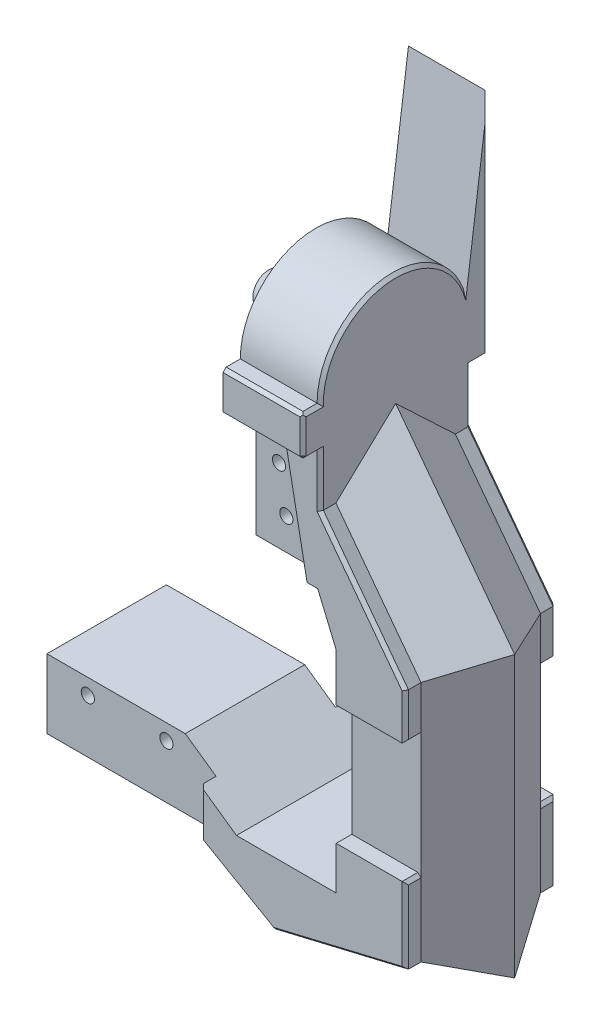
SolidWorks part; units mm, degrees
ref_plane "前视基准面" through (0, 0, 0) normal (0, 0, 1) x (1, 0, 0)
ref_plane "上视基准面" through (0, 0, 0) normal (0, 1, 0) x (1, 0, 0)
ref_plane "右视基准面" through (0, 0, 0) normal (1, 0, 0) x (0, 0, -1)
other "Configuration Table"
sketch "草图1" plane through (0, 0, 0) normal (0, 0, 1) x (1, 0, 0)
  line L0 (0, 0) -> (53.8, 0)
  line L1 (53.8, 0) -> (77, -13.3945)
  line L2 (77, -13.3945) -> (119, -3.4144)
  line L3 (119, -3.4144) -> (119, 73.5856)
  line L4 (119, 73.5856) -> (91.9365, 109.5)
  line L5 (91.9365, 109.5) -> (91.9365, 158)
  line L6 (91.9365, 158) -> (66.5044, 158)
  line L7 (66.5044, 158) -> (66.5044, 88)
  line L8 (66.5044, 88) -> (91.1544, 88)
  line L9 (91.1544, 88) -> (97, 74.0856)
  line L12 (65.3, 7.0856) -> (44, 22)
  line L13 (44, 22) -> (0, 22)
  line L14 (0, 22) -> (0, 0)
  line L15 (65.3, 7.0856) -> (97, 7.0856)
  line L16 (97, 7.0856) -> (97, 74.0856)
  circle A0 centre (73.8244, 111.53) radius 2.1
  circle A1 centre (76.1544, 98.03) radius 2.1
  circle A2 centre (13, 17) radius 2.1
  circle A3 centre (38, 17) radius 2.1
  dimension "D21" = 4.2
  dimension "D24" = 4.2
  dimension "D29" = 4.2
  dimension "D30" = 4.2
  dimension "D1" = 44
  dimension "D2" = 53
  dimension "D3" = 22
  dimension "D4" = 145
  dimension "D5" = 150
  dimension "D6" = 31.7
  dimension "D7" = 22
  dimension "D8" = 23.2
  dimension "D9" = 42
  dimension "D10" = 10.5
  dimension "D11" = 24.65
  dimension "D12" = 66
  dimension "D13" = 67.212
  dimension "D14" = 77
  dimension "D15" = 67
  dimension "D16" = 70
  dimension "D17" = 48.5
  dimension "D18" = 143
  dimension "D19" = 7.32
  dimension "D20" = 23.53
  dimension "D22" = 9.65
  dimension "D23" = 10.03
  dimension "D25" = 13
  dimension "D26" = 38
  dimension "D27" = 17
  dimension "D28" = 17
extrude "凸台-拉伸1" add sketch "草图1" along normal blind 38
sketch "草图2" plane through (91.9365, 0, 0) normal (1, 0, 0) x (0, 0, -1)
  line L0 (-38, 109.5) -> (-38, 158) construction
  line L1 (-38, 158) -> (0, 158) construction
  line L2 (0, 109.5) -> (0, 158) construction
  line L3 (-19, 109.5) -> (-19, 164.3174) construction
  line L5 (-38, 139) -> (-38, 158)
  line L6 (-38, 158) -> (0, 158)
  line L7 (0, 158) -> (0, 139)
  arc A0 (-38, 139) -> (0, 139) centre (-19, 139) cw
  circle A1 centre (-19, 139) radius 3
  line M6 (0, 109.5) -> (0, 158)
  line M7 (0, 158) -> (-38, 158)
  line M8 (-38, 158) -> (-38, 109.5)
  dimension "D1" = 6
extrude "切除-拉伸1" cut sketch "草图2" against normal through all contours A0 L6 M8 | A0 M7 M6 region at (91.9365, 153.756, 4.244) region at (91.9365, 153.756, 33.756)
sketch "草图3" plane through (66.5044, 0, 0) normal (-1, 0, 0) x (0, 0, 1)
  line L3 (0, 139) -> (0, 88)
  line L4 (0, 88) -> (38, 88)
  line L5 (38, 88) -> (38, 139)
  line L6 (0, 139) -> (0, 88)
  line L7 (0, 88) -> (38, 88)
  line L8 (38, 88) -> (38, 139)
  circle A0 centre (19, 139) radius 3
  arc A1 (38, 139) -> (0, 139) centre (19, 139) ccw
  arc A2 (38, 139) -> (0, 139) centre (19, 139) ccw
  dimension "D2" = 6
  dimension "D1" = 0
extrude "切除-拉伸3" cut sketch "草图3" against normal blind 1 contours A0
ref_plane "基准面1" through (77, 0, 0) normal (-1, 0, 0) x (0, 0, 1)
sketch "草图4" plane through (77, 0, 0) normal (-1, 0, 0) x (0, 0, 1)
  line L0 (38, -13.3945) -> (0, -13.3945) construction
  line L1 (38, -13.3945) -> (0, -13.3945)
  line L2 (0, -13.3945) -> (19, -24.4851)
  line L3 (19, -24.4851) -> (38, -13.3945)
  dimension "D1" = 22
ref_plane "基准面2" through (0, 109.5, 0) normal (0, -1, 0) x (-1, 0, 0)
sketch "草图9" plane through (0, 109.5, 0) normal (0, -1, 0) x (-1, 0, 0)
  line L0 (-91.9365, -38) -> (-91.9365, 0) construction
  line L1 (-91.9365, -38) -> (-91.9365, 0)
sketch "草图10" plane through (0, 109.5, 0) normal (0, -1, 0) x (-1, 0, 0)
  line L0 (-91.9365, 0) -> (-103.0271, -19)
  line L1 (-103.0271, -19) -> (-91.9365, -38)
  line L2 (-91.9365, 0) -> (-91.9365, -38)
  dimension "D1" = 22
ref_plane "基准面3" through (0, 0, 19) normal (0, 0, 1) x (1, 0, 0)
sketch "草图13" plane through (0, 0, 19) normal (0, 0, 1) x (1, 0, 0)
  line L3 (77, -13.3945) -> (119, -3.4144) construction
  line L10 (91.9365, 127.4291) -> (129.79, 77.1959)
  line L11 (129.79, 77.1959) -> (129.79, -11.941)
  line L12 (129.79, -11.941) -> (77, -24.4851)
  line L13 (119, 73.5856) -> (91.9365, 109.5) construction
  line L14 (91.9365, 109.5) -> (91.9365, 139) construction
  line L15 (119, 73.5856) -> (91.9365, 109.5)
  line L16 (91.9365, 109.5) -> (91.9365, 139)
  line L17 (77, -13.3945) -> (77, -24.4851) construction
  line L18 (119, -3.4144) -> (119, 73.5856) construction
  dimension "D1" = 10.79
  dimension "D2" = 10.79
  dimension "D3" = 10.7901
sweep "扫描3" add profiles "草图4" path "草图13"
sketch "草图14" plane through (0, 0, 38) normal (0, 0, 1) x (1, 0, 0)
  line L0 (66.5044, 126.1486) -> (80.4341, 126.1486)
  line L1 (80.4341, 126.1486) -> (87.7424, 88)
  line L2 (97, 58.8709) -> (118.9999, 58.8709)
  line L3 (97, 20.7689) -> (118.9999, 20.7689)
  line L4 (53.8, 0) -> (53.8, 15.138)
  line L15 (91.9365, 109.4998) -> (91.9365, 139)
  line L16 (91.9365, 139) -> (66.5044, 139)
  line L17 (66.5044, 139) -> (66.5044, 88)
  line L18 (66.5044, 88) -> (91.1544, 88)
  line L19 (91.1544, 88) -> (97, 74.0856)
  line L20 (97, 74.0856) -> (97, 7.0856)
  line L21 (97, 7.0856) -> (65.3, 7.0856)
  line L22 (65.3, 7.0856) -> (44, 22)
  line L23 (44, 22) -> (0, 22)
  line L24 (0, 22) -> (0, 0)
  line L25 (0, 0) -> (53.8, 0)
  line L26 (53.8, 0) -> (77, -13.3945)
  line L27 (77, -13.3945) -> (118.9999, -3.4144)
  line L28 (118.9999, -3.4144) -> (118.9999, 73.5855)
  line L29 (118.9999, 73.5855) -> (91.9365, 109.4998)
  line L30 (91.9365, 109.4998) -> (91.9365, 139)
  line L31 (91.9365, 139) -> (66.5044, 139)
  line L32 (66.5044, 139) -> (66.5044, 88)
  line L33 (66.5044, 88) -> (91.1544, 88)
  line L34 (91.1544, 88) -> (97, 74.0856)
  line L35 (97, 74.0856) -> (97, 7.0856)
  line L36 (97, 7.0856) -> (65.3, 7.0856)
  line L37 (65.3, 7.0856) -> (44, 22)
  line L38 (44, 22) -> (0, 22)
  line L39 (0, 22) -> (0, 0)
  line L40 (0, 0) -> (53.8, 0)
  line L41 (53.8, 0) -> (77, -13.3945)
  line L42 (77, -13.3945) -> (118.9999, -3.4144)
  line L43 (118.9999, -3.4144) -> (118.9999, 73.5855)
  line L44 (118.9999, 73.5855) -> (91.9365, 109.4998)
  line M16 (91.9365, 109.4998) -> (91.9365, 139)
  line M17 (91.9365, 139) -> (66.5044, 139)
  line M18 (66.5044, 139) -> (66.5044, 88)
  line M19 (66.5044, 88) -> (91.1544, 88)
  line M20 (91.1544, 88) -> (97, 74.0856)
  line M21 (97, 74.0856) -> (97, 7.0856)
  line M22 (97, 7.0856) -> (65.3, 7.0856)
  line M27 (53.8, 0) -> (77, -13.3945)
  line M28 (77, -13.3945) -> (118.9999, -3.4144)
  line M29 (118.9999, -3.4144) -> (118.9999, 73.5855)
  line M30 (118.9999, 73.5855) -> (91.9365, 109.4998)
  dimension "D1" = 0
extrude "凸台-拉伸2" add sketch "草图14" along normal blind 5 contours L3 M22 M27 M28 M29 M21 | L2 L0 L1 M21 M29 M30 M16 M17 M18 M19 M20 region at (94.8648, 97.4527, 38) region at (90.2976, 2.9827, 38)
sketch "草图15" plane through (0, 0, 0) normal (0, 0, -1) x (-1, 0, 0)
  line L0 (-53.8, 0) -> (-53.8, 15.138) construction
  line L1 (-97, 20.7689) -> (-118.9999, 20.7689) construction
  line L2 (-97, 58.8709) -> (-118.9999, 58.8709) construction
  line L3 (-80.4341, 126.1486) -> (-87.7424, 88) construction
  line L4 (-66.5044, 126.1486) -> (-80.4341, 126.1486) construction
  line L5 (-53.8, 0) -> (-53.8, 15.138)
  line L6 (-97, 20.7689) -> (-118.9999, 20.7689)
  line L7 (-97, 58.8709) -> (-118.9999, 58.8709)
  line L8 (-80.4341, 126.1486) -> (-87.7424, 88)
  line L9 (-66.5044, 126.1486) -> (-80.4341, 126.1486)
  line L15 (-91.9365, 139) -> (-91.9365, 109.4998)
  line L16 (-91.9365, 109.4998) -> (-118.9999, 73.5855)
  line L17 (-118.9999, 73.5855) -> (-118.9999, -3.4144)
  line L18 (-118.9999, -3.4144) -> (-77, -13.3945)
  line L19 (-77, -13.3945) -> (-53.8, 0)
  line L20 (-53.8, 0) -> (0, 0)
  line L21 (0, 0) -> (0, 22)
  line L22 (0, 22) -> (-44, 22)
  line L23 (-44, 22) -> (-65.3, 7.0856)
  line L24 (-65.3, 7.0856) -> (-97, 7.0856)
  line L25 (-97, 7.0856) -> (-97, 74.0856)
  line L26 (-97, 74.0856) -> (-91.1544, 88)
  line L27 (-91.1544, 88) -> (-66.5044, 88)
  line L28 (-66.5044, 88) -> (-66.5044, 139)
  line L29 (-66.5044, 139) -> (-91.9365, 139)
  line L30 (-91.9365, 139) -> (-91.9365, 109.4998)
  line L31 (-91.9365, 109.4998) -> (-118.9999, 73.5855)
  line L32 (-118.9999, 73.5855) -> (-118.9999, -3.4144)
  line L33 (-118.9999, -3.4144) -> (-77, -13.3945)
  line L34 (-77, -13.3945) -> (-53.8, 0)
  line L35 (-53.8, 0) -> (0, 0)
  line L36 (0, 0) -> (0, 22)
  line L37 (0, 22) -> (-44, 22)
  line L38 (-44, 22) -> (-65.3, 7.0856)
  line L39 (-65.3, 7.0856) -> (-97, 7.0856)
  line L40 (-97, 7.0856) -> (-97, 74.0856)
  line L41 (-97, 74.0856) -> (-91.1544, 88)
  line L42 (-91.1544, 88) -> (-66.5044, 88)
  line L43 (-66.5044, 88) -> (-66.5044, 139)
  line L44 (-66.5044, 139) -> (-91.9365, 139)
  line M16 (-91.9365, 139) -> (-91.9365, 109.4998)
  line M17 (-91.9365, 109.4998) -> (-118.9999, 73.5855)
  line M18 (-118.9999, 73.5855) -> (-118.9999, -3.4144)
  line M19 (-118.9999, -3.4144) -> (-77, -13.3945)
  line M20 (-77, -13.3945) -> (-53.8, 0)
  line M24 (-44, 22) -> (-65.3, 7.0856)
  line M25 (-65.3, 7.0856) -> (-97, 7.0856)
  line M26 (-97, 7.0856) -> (-97, 74.0856)
  line M27 (-97, 74.0856) -> (-91.1544, 88)
  line M28 (-91.1544, 88) -> (-66.5044, 88)
  line M29 (-66.5044, 88) -> (-66.5044, 139)
  line M30 (-66.5044, 139) -> (-91.9365, 139)
  dimension "D1" = 0
extrude "凸台-拉伸3" add sketch "草图15" along normal blind 5 contours L9 L7 L8 M29 M30 M16 M17 M18 M26 M27 M28 | L6 L5 M26 M18 M19 M20 M24 M25 region at (90.2976, 2.9827, 0) region at (94.8648, 97.4527, 0)
sketch "草图16" plane through (91.9365, 0, 0) normal (1, 0, 0) x (0, 0, -1)
  line L0 (-43, 109.4998) -> (-43, 139) construction
  arc A0 (-43, 139) -> (5, 139) centre (-19, 139) cw
extrude "拉伸-薄壁2" add sketch "草图16" along direction (1, 0, 0) on the side against the normal up to surface (25.4322 mm away) thin up to face at (66.5044, 136, 19) thin type one direction wall 10
sketch "草图17" plane through (91.9365, 0, 0) normal (1, 0, 0) x (0, 0, -1)
  line L0 (5, 128.4582) -> (10.5, 128.4582)
  line L3 (10.5, 128.4582) -> (10.5, 198.4582)
  line L4 (10.5, 198.4582) -> (3.6023, 147.0707)
  line L6 (-43, 139) -> (-43, 109.4998)
  line L7 (-43, 109.4998) -> (-38, 109.4998)
  line L8 (-38, 109.4998) -> (-19, 127.4291)
  line L9 (-19, 127.4291) -> (0, 109.4998)
  line L10 (0, 109.4998) -> (5, 109.4998)
  line L11 (5, 109.4998) -> (5, 139)
  line L12 (-43, 139) -> (-43, 109.4998)
  line L13 (-43, 109.4998) -> (-38, 109.4998)
  line L14 (-38, 109.4998) -> (-19, 127.4291)
  line L15 (-19, 127.4291) -> (0, 109.4998)
  line L16 (0, 109.4998) -> (5, 109.4998)
  line L17 (5, 109.4998) -> (5, 139)
  arc A1 (5, 139) -> (-43, 139) centre (-19, 139) ccw
  arc A2 (5, 139) -> (-43, 139) centre (-19, 139) ccw
  arc M10 (5, 139) -> (-43, 139) centre (-19, 139) ccw
  line M16 (5, 109.4998) -> (5, 139)
  dimension "D2" = 5.5
  dimension "D3" = 70
  dimension "D1" = 0
extrude "凸台-拉伸7" add sketch "草图17" against normal up to surface (25.4322 mm away) contours L3 L4 L0 M10 M16 region at (91.9365, 154.397, -7.9904) up to face at (66.5044, 122.8243, 19)
sketch "草图18" plane through (0, 128.4582, 0) normal (0, -1, 0) x (1, 0, 0)
  line L4 (66.5044, -5) -> (66.5044, -10.5)
  line L5 (66.5044, -10.5) -> (91.9365, -10.5)
  line L6 (91.9365, -10.5) -> (91.9365, -5)
  line L7 (91.9365, -5) -> (66.5044, -5)
  line L8 (66.5044, -5) -> (66.5044, -10.5)
  line L9 (66.5044, -10.5) -> (91.9365, -10.5)
  line L10 (91.9365, -10.5) -> (91.9365, -5)
  line L11 (91.9365, -5) -> (66.5044, -5)
  dimension "D1" = 0
extrude "凸台-拉伸8" add sketch "草图18" along normal up to surface (2.3096 mm away) up to face at (73.4692, 126.1486, -2.5)
sketch "草图19" plane through (0, 0, 43) normal (0, 0, 1) x (1, 0, 0)
  line L0 (80.4341, 126.1486) -> (91.9365, 126.1486)
  line L11 (97, 74.0856) -> (97, 58.8709)
  line L12 (97, 58.8709) -> (118.9999, 58.8709)
  line L13 (118.9999, 58.8709) -> (118.9999, 73.5855)
  line L14 (118.9999, 73.5855) -> (91.9365, 109.4998)
  line L15 (91.9365, 109.4998) -> (91.9365, 139)
  line L16 (91.9365, 139) -> (66.5044, 139)
  line L17 (66.5044, 139) -> (66.5044, 126.1486)
  line L18 (66.5044, 126.1486) -> (80.4341, 126.1486)
  line L19 (80.4341, 126.1486) -> (87.7424, 88)
  line L20 (87.7424, 88) -> (91.1544, 88)
  line L21 (91.1544, 88) -> (97, 74.0856)
  line L26 (91.9365, 126.1486) -> (91.9365, 139)
  line L27 (91.9365, 139) -> (66.5044, 139)
  line L28 (66.5044, 139) -> (66.5044, 126.1486)
  line L29 (66.5044, 126.1486) -> (80.4341, 126.1486)
  line L31 (87.7424, 88) -> (91.1544, 88)
  line M16 (91.9365, 109.4998) -> (91.9365, 139)
  line M17 (91.9365, 139) -> (66.5044, 139)
  line M18 (66.5044, 139) -> (66.5044, 126.1486)
  line M19 (66.5044, 126.1486) -> (80.4341, 126.1486)
  dimension "D1" = 0
extrude "凸台-拉伸10" add sketch "草图19" along normal blind 5.5 contours L0 M19 M16 M17 M18 region at (79.2205, 132.5743, 43)
sketch "草图20" plane through (66.5044, 0, 0) normal (-1, 0, 0) x (0, 0, 1)
  line L9 (-10.5, 198.4582) -> (-10.5, 126.1486)
  line L10 (-10.5, 126.1486) -> (0, 126.1486)
  line L11 (0, 126.1486) -> (0, 88)
  line L12 (0, 88) -> (38, 88)
  line L13 (38, 88) -> (38, 126.1486)
  line L14 (38, 126.1486) -> (48.5, 126.1486)
  line L15 (48.5, 126.1486) -> (48.5, 139)
  line L16 (48.5, 139) -> (43, 139)
  line L17 (-3.6023, 147.0707) -> (-10.5, 198.4582)
  line L18 (-10.5, 198.4582) -> (-10.5, 126.1486)
  line L19 (-10.5, 126.1486) -> (0, 126.1486)
  line L20 (0, 126.1486) -> (0, 88)
  line L21 (0, 88) -> (38, 88)
  line L22 (38, 88) -> (38, 126.1486)
  line L23 (38, 126.1486) -> (48.5, 126.1486)
  line L24 (48.5, 126.1486) -> (48.5, 139)
  line L25 (48.5, 139) -> (43, 139)
  line L26 (-3.6023, 147.0707) -> (-10.5, 198.4582)
  circle A0 centre (19, 139) radius 3 construction
  arc A1 (43, 139) -> (-3.6023, 147.0707) centre (19, 139) ccw
  arc A2 (43, 139) -> (-3.6023, 147.0707) centre (19, 139) ccw
  circle A3 centre (19, 139) radius 3
  circle A4 centre (19, 139) radius 13
  dimension "D2" = 26
  dimension "D1" = 0
ref_plane "基准面4" through (51.5044, 0, 0) normal (-1, 0, 0) x (0, 0, 1)
sketch "草图21" plane through (51.5044, 0, 0) normal (-1, 0, 0) x (0, 0, 1)
  circle A0 centre (19, 139) radius 13 construction
  circle A1 centre (19, 139) radius 3 construction
  circle A2 centre (19, 139) radius 13
  circle A3 centre (19, 139) radius 3
  circle A4 centre (19, 139) radius 5
  dimension "D1" = 10
loft "放样1" add section "草图21" section "草图20" connector at (51.5044, 140.2647, 23.8374) connector at (66.5044, 141.5722, 31.743)
sketch "草图23" plane through (51.5044, 0, 0) normal (-1, 0, 0) x (0, 0, 1)
  circle A0 centre (19, 139) radius 3.15
  circle A1 centre (19, 139) radius 5
  circle A2 centre (19, 139) radius 5
  dimension "D2" = 6.3
  dimension "D1" = 0
extrude "切除-拉伸4" cut sketch "草图23" against normal blind 15 contours A0
chamfer "倒角1" distance 1 angle 45 1 edges at (79.2205, 139, 48.5)
chamfer "倒角3" distance 1 angle 45 25 edges at (118.9999, 58.8709, -2.5) (118.9999, 66.2282, -5) (105.4682, 91.5427, -5) (91.9365, 117.8242, -5) (91.9365, 126.1486, -7.75) (91.9365, 162.3034, -10.5) (91.9365, 162.648, 23.0954) (91.9365, 139, 45.25) (79.2205, 126.1486, 48.5) (118.9999, 58.8709, 40.5) (91.9365, 132.0743, 48.5) (91.9365, 126.1486, 45.75) (91.9365, 117.8242, 43) (105.4682, 91.5427, 43) (118.9999, 66.2282, 43) (118.9999, 20.7689, -2.5) (118.9999, 8.6772, -5) (98, -8.4045, -5) (65.4, -6.6973, -5) (53.8, 7.569, -5) (118.9999, 20.7689, 40.5) (118.9999, 8.6772, 43) (98, -8.4045, 43) (65.4, -6.6973, 43) (53.8, 7.569, 43)
